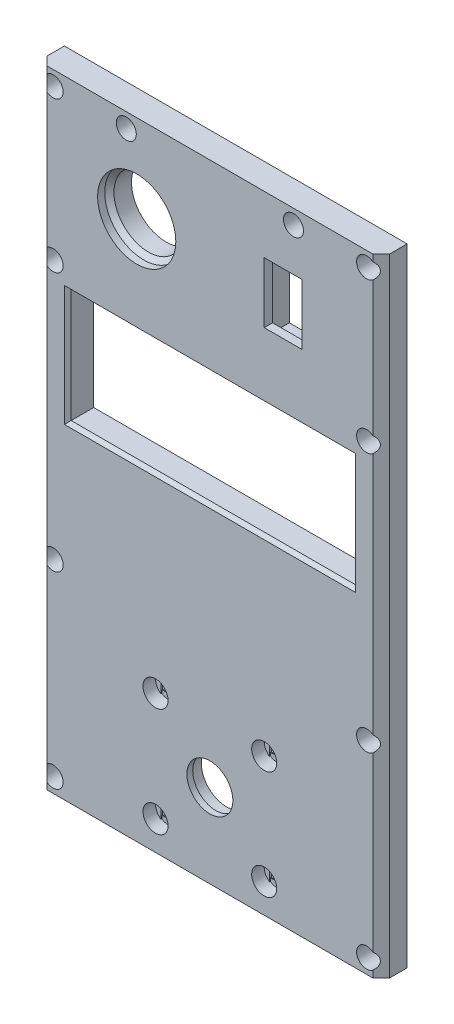
SolidWorks part; units mm, degrees
ref_plane "Front Plane" through (0, 0, 0) normal (0, 0, 1) x (1, 0, 0)
ref_plane "Top Plane" through (0, 0, 0) normal (0, 1, 0) x (1, 0, 0)
ref_plane "Right Plane" through (0, 0, 0) normal (1, 0, 0) x (0, 0, -1)
sketch "Sketch1" plane through (0, 0, 0) normal (0, 0, 1) x (1, 0, 0)
  line L1 (-41, -75) -> (41, -75)
  line L2 (-41, -75) -> (-41, 75)
  line L3 (-41, 75) -> (41, 75)
  line L4 (41, -75) -> (41, 75)
  line L5 (-41, -75) -> (41, 75) construction
  line L6 (-41, 75) -> (41, -75) construction
  line L7 (-34, -68) -> (34, -68)
  line L8 (-34, -68) -> (-34, 68)
  line L9 (-34, 68) -> (34, 68)
  line L10 (34, -68) -> (34, 68)
  line L11 (-34, -68) -> (34, 68) construction
  line L12 (-34, 68) -> (34, -68) construction
  point P0 (0, 0)
  point P6 (0, 0)
  dimension "D1" = 150
  dimension "D2" = 82
  dimension "D3" = 7
  dimension "D4" = 7
extrude "Boss-Extrude1" add sketch "Sketch1" along normal blind 7
sketch "Sketch2" plane through (0, 0, 7) normal (0, 0, 1) x (1, 0, 0)
  line L0 (34, -68) -> (34, 68) construction
  line L1 (-34, -68) -> (34, -68)
  line L2 (-34, -68) -> (-34, -32)
  line L3 (-34, -32) -> (34, -32)
  line L4 (34, -68) -> (34, -32)
  dimension "D1" = 36
extrude "Boss-Extrude2" add sketch "Sketch2" against normal up to surface (7 mm away) up to face at (0, 0, 0)
sketch "Sketch3" plane through (0, 0, 0) normal (0, 0, -1) x (-1, 0, 0)
  line L0 (0, -75) -> (0, -55) construction
  line L1 (41, -75) -> (-41, -75) construction
  circle A0 centre (0, -55) radius 5.5
  dimension "D1" = 11
  dimension "D2" = 20
extrude "Cut-Extrude1" cut sketch "Sketch3" against normal through all
sketch "Sketch4" plane through (0, 0, 0) normal (0, 0, -1) x (-1, 0, 0)
  circle A0 centre (0, -55) radius 6.05
  dimension "D1" = 12.1
extrude "Cut-Extrude2" cut sketch "Sketch4" against normal offset from surface (5.6 mm away) 1.4 up to face at (-5.5, -55, 7)
sketch "Sketch5" plane through (0, 0, 0) normal (0, 0, -1) x (-1, 0, 0)
  circle A0 centre (0, -55) radius 11
  dimension "D1" = 22
extrude "Cut-Extrude3" cut sketch "Sketch5" against normal offset from surface (3 mm away) 2.6 up to face at (-6.05, -55, 5.6)
sketch "Sketch6" plane through (0, 0, 0) normal (0, 0, -1) x (-1, 0, 0)
  line L1 (-13, -68) -> (13, -68) construction
  line L2 (-13, -68) -> (-13, -42) construction
  line L3 (-13, -42) -> (13, -42) construction
  line L4 (13, -68) -> (13, -42) construction
  line L5 (-13, -68) -> (13, -42) construction
  line L6 (-13, -42) -> (13, -68) construction
  circle A0 centre (-13, -42) radius 1.7
  circle A1 centre (13, -42) radius 1.7
  circle A2 centre (13, -68) radius 1.7
  circle A3 centre (-13, -68) radius 1.7
  point P0 (0, -55)
  dimension "D2" = 3.4
  dimension "D1" = 26
extrude "Cut-Extrude4" cut sketch "Sketch6" against normal through all
sketch "Sketch7" plane through (0, 0, 0) normal (0, 0, -1) x (-1, 0, 0)
  line L1 (-25, -74) -> (25, -74)
  line L2 (-25, -74) -> (-25, -36)
  line L3 (-25, -36) -> (25, -36)
  line L4 (25, -74) -> (25, -36)
  line L5 (-25, -74) -> (25, -36) construction
  line L6 (-25, -36) -> (25, -74) construction
  point P0 (0, -55)
  dimension "D1" = 50
  dimension "D2" = 38
extrude "Cut-Extrude5" cut sketch "Sketch7" against normal blind 1
sketch "Sketch8" plane through (0, 0, 7) normal (0, 0, 1) x (1, 0, 0)
  circle A0 centre (-13, -42) radius 3
  circle A1 centre (13, -42) radius 3
  circle A2 centre (13, -68) radius 3
  circle A3 centre (-13, -68) radius 3
  dimension "D1" = 6
extrude "Cut-Extrude6" cut sketch "Sketch8" against normal blind 3
sketch "Sketch9" plane through (0, 0, 7) normal (0, 0, 1) x (1, 0, 0)
  line L0 (-41, 75) -> (-41, -75) construction
  line L1 (-37.5, -71.5) -> (37.5, -71.5) construction
  line L2 (-37.5, -71.5) -> (-37.5, 71.5) construction
  line L3 (-37.5, 71.5) -> (37.5, 71.5) construction
  line L4 (37.5, -71.5) -> (37.5, 71.5) construction
  line L5 (-37.5, -71.5) -> (37.5, 71.5) construction
  line L6 (-37.5, 71.5) -> (37.5, -71.5) construction
  line L7 (41, 75) -> (-41, 75) construction
  circle A0 centre (-37.5, 71.5) radius 1.45
  circle A1 centre (37.5, 71.5) radius 1.45
  circle A4 centre (-37.5, -71.5) radius 1.45
  circle A5 centre (37.5, -71.5) radius 1.45
  circle A6 centre (-37.5, 35.5) radius 1.45
  circle A7 centre (37.5, 35.5) radius 1.45
  circle A8 centre (37.5, -26.5) radius 1.45
  circle A9 centre (-37.5, -26.5) radius 1.45
  point P0 (0, 0)
  dimension "D3" = 2.9
  dimension "D1" = 3.5
  dimension "D2" = 3.5
  dimension "D4" = 45
  dimension "D5" = 36
extrude "Cut-Extrude7" cut sketch "Sketch9" against normal through all
sketch "Sketch10" plane through (0, 0, 7) normal (0, 0, 1) x (1, 0, 0)
  circle A0 centre (-37.5, 71.5) radius 2.4
  circle A1 centre (37.5, 35.5) radius 2.4
  circle A2 centre (-37.5, 35.5) radius 2.4
  circle A3 centre (37.5, 71.5) radius 2.4
  circle A4 centre (-37.5, -71.5) radius 2.4
  circle A5 centre (37.5, -71.5) radius 2.4
  circle A6 centre (-37.5, -26.5) radius 2.4
  circle A7 centre (37.5, -26.5) radius 2.4
  dimension "D1" = 4.8
extrude "Cut-Extrude8" cut sketch "Sketch10" against normal blind 5
chamfer "Chamfer1" distance 2 angle 45 2 edges at (-41, 0, 7) (41, 0, 7)
sketch "Sketch11" plane through (0, 0, 7) normal (0, 0, 1) x (1, 0, 0)
  line L0 (34, -32) -> (34, 68) construction
  line L1 (-34, -32) -> (34, -32)
  line L2 (-34, -32) -> (-34, 3.6)
  line L3 (-34, 3.6) -> (34, 3.6)
  line L4 (34, -32) -> (34, 3.6)
  line L5 (-39, -75) -> (39, -75) construction
  dimension "D1" = 78.6
extrude "Boss-Extrude3" add sketch "Sketch11" against normal up to surface (7 mm away) up to face at (-36.05, -71.5, 0)
sketch "Sketch12" plane through (0, 0, 7) normal (0, 0, 1) x (1, 0, 0)
  line L0 (-37.5, 71.5) -> (37.5, 71.5) construction
  line L1 (-20, 71.5) -> (20, 71.5) construction
  circle A0 centre (-20, 71.5) radius 1.45
  circle A1 centre (20, 71.5) radius 1.45
  circle A2 centre (-37.5, 71.5) radius 1.45 construction
  point P7 (0, 71.5)
  dimension "D1" = 40
extrude "Cut-Extrude9" cut sketch "Sketch12" against normal through all
sketch "Sketch13" plane through (0, 0, 7) normal (0, 0, 1) x (1, 0, 0)
  circle A0 centre (-20, 71.5) radius 2.4
  circle A1 centre (20, 71.5) radius 2.4
  circle A2 centre (-37.5, 71.5) radius 2.4 construction
extrude "Cut-Extrude10" cut sketch "Sketch13" against normal up to surface (5 mm away) up to face at (-35.1, 71.5, 2)
chamfer "Chamfer2" distance 0.8 angle 45 12 edges at (0, -75, 0) (-41, 0, 0) (0, 75, 0) (41, 0, 0) (34, 35.8, 7) (0, 68, 7) (-34, 35.8, 7) (0, 3.6, 7) (-34, 35.8, 0) (0, 68, 0) (34, 35.8, 0) (0, 3.6, 0)
sketch "Sketch14" plane through (0, 0, 2) normal (0, 0, 1) x (1, 0, 0)
  line L2 (-38.95, -28.4125) -> (-38.95, -24.5875)
  line L4 (-36.05, -28.4125) -> (-36.05, -24.5875)
  line L5 (-38.95, -28.4125) -> (-36.05, -24.5875) construction
  line L6 (-38.95, -24.5875) -> (-36.05, -28.4125) construction
  line L14 (-38.95, -73.4125) -> (-38.95, -69.5875)
  line L16 (-36.05, -73.4125) -> (-36.05, -69.5875)
  line L17 (-38.95, -73.4125) -> (-36.05, -69.5875) construction
  line L18 (-38.95, -69.5875) -> (-36.05, -73.4125) construction
  line L26 (-38.95, 33.5875) -> (-38.95, 37.4125)
  line L28 (-36.05, 33.5875) -> (-36.05, 37.4125)
  line L29 (-38.95, 33.5875) -> (-36.05, 37.4125) construction
  line L30 (-38.95, 37.4125) -> (-36.05, 33.5875) construction
  line L32 (-21.45, 69.5875) -> (-21.45, 73.4125)
  line L34 (-18.55, 69.5875) -> (-18.55, 73.4125)
  line L35 (-21.45, 69.5875) -> (-18.55, 73.4125) construction
  line L36 (-21.45, 73.4125) -> (-18.55, 69.5875) construction
  line L38 (-38.95, 69.5875) -> (-38.95, 73.4125)
  line L40 (-36.05, 69.5875) -> (-36.05, 73.4125)
  line L41 (-38.95, 69.5875) -> (-36.05, 73.4125) construction
  line L42 (-38.95, 73.4125) -> (-36.05, 69.5875) construction
  arc A0 (-39, -28.3735) -> (-39, -24.6265) centre (-37.5, -26.5) ccw construction
  circle A2 centre (-37.5, -71.5) radius 2.4 construction
  circle A4 centre (-37.5, 35.5) radius 2.4 construction
  circle A5 centre (-20, 71.5) radius 2.4 construction
  circle A6 centre (-37.5, 71.5) radius 2.4 construction
  circle A7 centre (-37.5, 71.5) radius 1.45 construction
  circle A8 centre (-20, 71.5) radius 1.45 construction
  circle A9 centre (-37.5, 35.5) radius 1.45 construction
  circle A10 centre (-37.5, -26.5) radius 1.45 construction
  circle A12 centre (-37.5, -71.5) radius 1.45 construction
  arc A16 (-21.45, 69.5875) -> (-18.55, 69.5875) centre (-20, 71.5) ccw
  arc A17 (-36.05, 73.4125) -> (-38.95, 73.4125) centre (-37.5, 71.5) ccw
  arc A18 (-36.05, 37.4125) -> (-38.95, 37.4125) centre (-37.5, 35.5) ccw
  arc A20 (-38.95, -28.4125) -> (-36.05, -28.4125) centre (-37.5, -26.5) ccw
  arc A22 (-36.05, -69.5875) -> (-38.95, -69.5875) centre (-37.5, -71.5) ccw
  arc A23 (-38.95, 69.5875) -> (-36.05, 69.5875) centre (-37.5, 71.5) ccw
  arc A24 (-18.55, 73.4125) -> (-21.45, 73.4125) centre (-20, 71.5) ccw
  arc A25 (-38.95, 33.5875) -> (-36.05, 33.5875) centre (-37.5, 35.5) ccw
  arc A26 (-36.05, -24.5875) -> (-38.95, -24.5875) centre (-37.5, -26.5) ccw
  arc A29 (-38.95, -73.4125) -> (-36.05, -73.4125) centre (-37.5, -71.5) ccw
  point P0 (-37.5, -26.5)
  point P17 (-37.5, -71.5)
  point P33 (-37.5, 35.5)
  point P41 (-20, 71.5)
  point P49 (-37.5, 71.5)
extrude "Cut-Extrude11" cut sketch "Sketch14" against normal blind 0.2
sketch "Sketch15" plane through (0, 0, 1.8) normal (0, 0, 1) x (1, 0, 0)
  line L0 (-36.05, -71.5) -> (-36.05, -69.5875) construction
  line L1 (-38.95, -72.95) -> (-36.05, -72.95)
  line L2 (-38.95, -72.95) -> (-38.95, -70.05)
  line L3 (-38.95, -70.05) -> (-36.05, -70.05)
  line L4 (-36.05, -72.95) -> (-36.05, -70.05)
  line L5 (-38.95, -72.95) -> (-36.05, -70.05) construction
  line L6 (-38.95, -70.05) -> (-36.05, -72.95) construction
  line L7 (-36.05, 35.5) -> (-36.05, 37.4125) construction
  line L8 (-38.95, -27.95) -> (-36.05, -27.95)
  line L9 (-38.95, -27.95) -> (-38.95, -25.05)
  line L10 (-38.95, -25.05) -> (-36.05, -25.05)
  line L11 (-36.05, -27.95) -> (-36.05, -25.05)
  line L12 (-38.95, -27.95) -> (-36.05, -25.05) construction
  line L13 (-38.95, -25.05) -> (-36.05, -27.95) construction
  line L14 (-38.95, 34.05) -> (-36.05, 34.05)
  line L15 (-38.95, 34.05) -> (-38.95, 36.95)
  line L16 (-38.95, 36.95) -> (-36.05, 36.95)
  line L17 (-36.05, 34.05) -> (-36.05, 36.95)
  line L18 (-38.95, 34.05) -> (-36.05, 36.95) construction
  line L19 (-38.95, 36.95) -> (-36.05, 34.05) construction
  line L20 (-36.05, 69.5875) -> (-36.05, 73.4125) construction
  line L21 (-38.95, 70.05) -> (-36.05, 70.05)
  line L22 (-38.95, 70.05) -> (-38.95, 72.95)
  line L23 (-38.95, 72.95) -> (-36.05, 72.95)
  line L24 (-36.05, 70.05) -> (-36.05, 72.95)
  line L25 (-38.95, 70.05) -> (-36.05, 72.95) construction
  line L26 (-38.95, 72.95) -> (-36.05, 70.05) construction
  line L27 (-18.55, 69.5875) -> (-18.55, 73.4125) construction
  line L28 (-21.45, 70.05) -> (-18.55, 70.05)
  line L29 (-21.45, 70.05) -> (-21.45, 72.95)
  line L30 (-21.45, 72.95) -> (-18.55, 72.95)
  line L31 (-18.55, 70.05) -> (-18.55, 72.95)
  line L32 (-21.45, 70.05) -> (-18.55, 72.95) construction
  line L33 (-21.45, 72.95) -> (-18.55, 70.05) construction
  arc A0 (-36.05, -26.5) -> (-38.95, -26.5) centre (-37.5, -26.5) ccw construction
  arc A1 (-36.05, 35.5) -> (-38.95, 35.5) centre (-37.5, 35.5) ccw construction
  arc A2 (-18.55, 71.5) -> (-21.45, 71.5) centre (-20, 71.5) ccw construction
  arc A3 (-36.05, 71.5) -> (-38.95, 71.5) centre (-37.5, 71.5) ccw construction
  point P0 (-37.5, -71.5)
  point P8 (-37.5, -26.5)
  point P17 (-37.5, 35.5)
  point P28 (-37.5, 71.5)
  point P36 (-20, 71.5)
extrude "Cut-Extrude12" cut sketch "Sketch15" against normal blind 0.2
sketch "Sketch16" plane through (0, 0, 4) normal (0, 0, 1) x (1, 0, 0)
  line L2 (-14.7, -44.4718) -> (-14.7, -39.5282)
  line L4 (-11.3, -44.4718) -> (-11.3, -39.5282)
  line L5 (-14.7, -44.4718) -> (-11.3, -39.5282) construction
  line L6 (-14.7, -39.5282) -> (-11.3, -44.4718) construction
  line L8 (-14.7, -70.4718) -> (-14.7, -65.5282)
  line L10 (-11.3, -70.4718) -> (-11.3, -65.5282)
  line L11 (-14.7, -70.4718) -> (-11.3, -65.5282) construction
  line L12 (-14.7, -65.5282) -> (-11.3, -70.4718) construction
  circle A0 centre (-13, -42) radius 3 construction
  circle A1 centre (-13, -68) radius 3 construction
  circle A2 centre (-13, -68) radius 1.7 construction
  circle A3 centre (-13, -42) radius 1.7 construction
  circle A4 centre (-13, -68) radius 3 construction
  circle A5 centre (-13, -42) radius 3 construction
  arc A6 (-11.3, -65.5282) -> (-14.7, -65.5282) centre (-13, -68) ccw
  arc A7 (-14.7, -44.4718) -> (-11.3, -44.4718) centre (-13, -42) ccw
  arc A8 (-11.3, -39.5282) -> (-14.7, -39.5282) centre (-13, -42) ccw
  arc A9 (-14.7, -70.4718) -> (-11.3, -70.4718) centre (-13, -68) ccw
  point P0 (-13, -42)
  point P8 (-13, -68)
extrude "Cut-Extrude13" cut sketch "Sketch16" against normal blind 0.2
sketch "Sketch17" plane through (0, 0, 3.8) normal (0, 0, 1) x (1, 0, 0)
  line L0 (-11.3, -44.4718) -> (-11.3, -39.5282) construction
  line L1 (-14.7, -43.7) -> (-11.3, -43.7)
  line L2 (-14.7, -43.7) -> (-14.7, -40.3)
  line L3 (-14.7, -40.3) -> (-11.3, -40.3)
  line L4 (-11.3, -43.7) -> (-11.3, -40.3)
  line L5 (-14.7, -43.7) -> (-11.3, -40.3) construction
  line L6 (-14.7, -40.3) -> (-11.3, -43.7) construction
  line L7 (-11.3, -70.4718) -> (-11.3, -65.5282) construction
  line L8 (-14.7, -69.7) -> (-11.3, -69.7)
  line L9 (-14.7, -69.7) -> (-14.7, -66.3)
  line L10 (-14.7, -66.3) -> (-11.3, -66.3)
  line L11 (-11.3, -69.7) -> (-11.3, -66.3)
  line L12 (-14.7, -69.7) -> (-11.3, -66.3) construction
  line L13 (-14.7, -66.3) -> (-11.3, -69.7) construction
  arc A0 (-11.3, -68) -> (-14.7, -68) centre (-13, -68) ccw construction
  arc A1 (-11.3, -42) -> (-14.7, -42) centre (-13, -42) ccw construction
  point P0 (-13, -42)
  point P8 (-13, -68)
extrude "Cut-Extrude14" cut sketch "Sketch17" against normal blind 0.2
mirror "Mirror1" about plane through (0, 0, 0) normal (1, 0, 0) of "Cut-Extrude12", "Cut-Extrude13", "Cut-Extrude14", "Cut-Extrude11"
sketch "Sketch18" plane through (0, 0, 7) normal (0, 0, 1) x (1, 0, 0)
  line L0 (34.8, 68.8) -> (34.8, 2.8) construction
  line L1 (-34.8, 68.8) -> (34.8, 68.8)
  line L2 (-34.8, 68.8) -> (-34.8, 30.8)
  line L3 (-34.8, 30.8) -> (34.8, 30.8)
  line L4 (34.8, 68.8) -> (34.8, 30.8)
  dimension "D1" = 38
extrude "Boss-Extrude4" add sketch "Sketch18" against normal up to surface (7 mm away) up to face at (0, 35.8, 0)
chamfer "Chamfer3" distance 0.8 angle 45 1 edges at (0, 30.8, 7)
sketch "Sketch19" plane through (0, 0, 7) normal (0, 0, 1) x (1, 0, 0)
  line L0 (17.5, 54) -> (-17.5, 54) construction
  line L1 (13, 46.75) -> (22, 46.75)
  line L2 (13, 46.75) -> (13, 61.25)
  line L3 (13, 61.25) -> (22, 61.25)
  line L4 (22, 46.75) -> (22, 61.25)
  line L5 (13, 46.75) -> (22, 61.25) construction
  line L6 (13, 61.25) -> (22, 46.75) construction
  circle A0 centre (-17.5, 54) radius 8.25
  point P2 (17.5, 54)
  point P8 (0, 54)
  dimension "D3" = 16.5
  dimension "D1" = 9
  dimension "D2" = 14.5
  dimension "D4" = 35
  dimension "D5" = 54
extrude "Cut-Extrude15" cut sketch "Sketch19" against normal through all
sketch "Sketch20" plane through (0, 0, 0) normal (0, 0, -1) x (-1, 0, 0)
  line L0 (-22, 61.25) -> (-13, 46.75) construction
  line L1 (-22, 61.25) -> (-13, 61.25) construction
  line L2 (-23, 43.75) -> (-12, 43.75)
  line L3 (-23, 43.75) -> (-23, 64.25)
  line L4 (-23, 64.25) -> (-12, 64.25)
  line L5 (-12, 43.75) -> (-12, 64.25)
  line L6 (-23, 43.75) -> (-12, 64.25) construction
  line L7 (-23, 64.25) -> (-12, 43.75) construction
  line L8 (-13, 61.25) -> (-13, 46.75) construction
  point P4 (-17.5, 54)
  dimension "D1" = 3
  dimension "D2" = 1
extrude "Cut-Extrude16" cut sketch "Sketch20" against normal offset from surface (5 mm away) 2 up to face at (-9.25, 54, 7)
sketch "Sketch21" plane through (0, 0, 7) normal (0, 0, 1) x (1, 0, 0)
  circle A0 centre (-17.5, 54) radius 9.35
  dimension "D1" = 18.7
extrude "Cut-Extrude17" cut sketch "Sketch21" against normal blind 1.6
chamfer "Chamfer4" distance 1.2 angle 45 1 edges at (-9.25, 54, 5.4)
